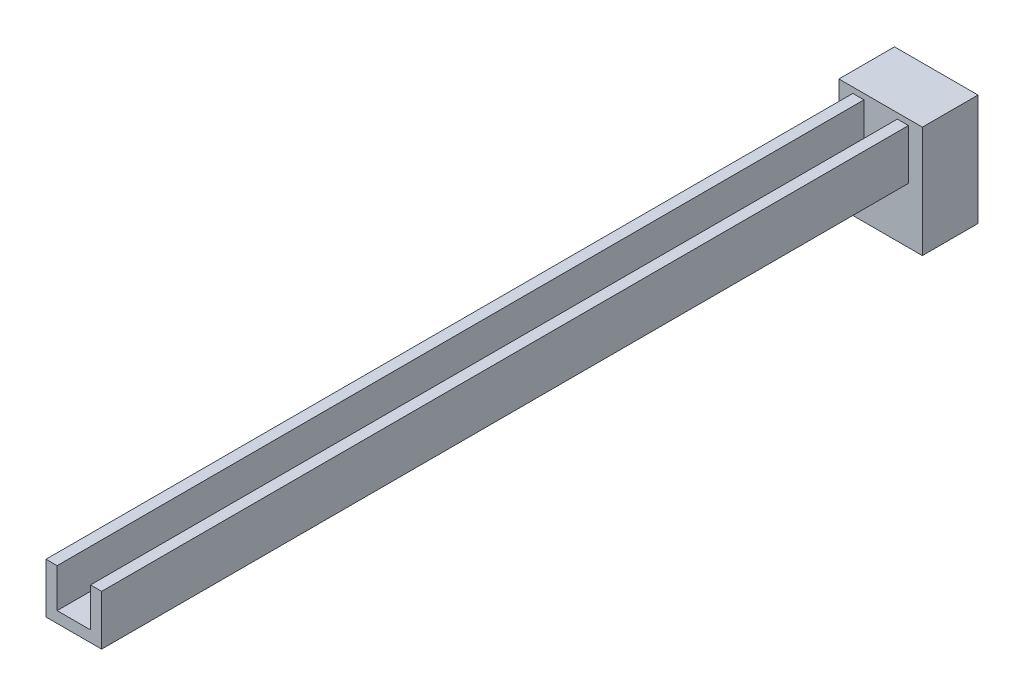
SolidWorks part; units mm, degrees
ref_plane "正面" through (0, 0, 0) normal (0, 0, 1) x (1, 0, 0)
ref_plane "平面" through (0, 0, 0) normal (0, 1, 0) x (1, 0, 0)
ref_plane "右側面" through (0, 0, 0) normal (1, 0, 0) x (0, 0, -1)
sketch "ｽｹｯﾁ1" plane through (0, 0, 0) normal (0, 0, 1) x (1, 0, 0)
  line L0 (-5, 9) -> (-5, 0)
  line L1 (-5, 0) -> (5, 0)
  line L2 (5, 0) -> (5, 9)
  line L3 (5, 9) -> (3, 9)
  line L4 (3, 9) -> (3, 2)
  line L5 (3, 2) -> (-3, 2)
  line L6 (-3, 2) -> (-3, 9)
  line L7 (-3, 9) -> (-5, 9)
  dimension "D1" = 9
  dimension "D2" = 9
  dimension "D3" = 10
  dimension "D4" = 5
  dimension "D5" = 2
  dimension "D6" = 2
  dimension "D7" = 2
extrude "ﾎﾞｽ - 押し出し1" add sketch "ｽｹｯﾁ1" along normal blind 245
sketch "ｽｹｯﾁ2" plane through (0, 0, 0) normal (0, -1, 0) x (1, 0, 0)
  line L0 (-5, 245) -> (5, 245) construction
  circle A0 centre (0, 225) radius 2.5
  circle A1 centre (0, 217) radius 2.5
  circle A2 centre (0, 122.5) radius 2.5
  circle A3 centre (0, 209) radius 2.5
  circle A4 centre (0, 193) radius 2.5
  circle A5 centre (0, 161) radius 2.5
  dimension "D1" = 20
  dimension "D3" = 5
  dimension "D4" = 5
  dimension "D5" = 5
  dimension "D6" = 122.5
  dimension "D7" = 5
  dimension "D8" = 8
  dimension "D9" = 5
  dimension "D10" = 16
  dimension "D11" = 5
  dimension "D12" = 32
  dimension "D2" = 28
extrude "ｶｯﾄ - 押し出し1" cut sketch "ｽｹｯﾁ2" against normal through all
ref_plane "平面1" through (0, 0, 122.5) normal (0, 0, 1) x (1, 0, 0)
mirror "ﾐﾗｰ1" about plane through (0, 0, 122.5) normal (0, 0, 1) of "ｶｯﾄ - 押し出し1"
sketch "ｽｹｯﾁ3" plane through (0, 0, 0) normal (0, -1, 0) x (1, 0, 0)
  line L0 (-5, 0) -> (-5, 100)
  line L1 (-5, 245) -> (-5, 0) construction
  line L2 (-5, 100) -> (5, 100)
  line L3 (5, 245) -> (5, 0) construction
  line L4 (5, 100) -> (5, 0)
  line L5 (5, 0) -> (-5, 0)
  dimension "D1" = 100
extrude "ｶｯﾄ - 押し出し2" cut sketch "ｽｹｯﾁ3" against normal through all both
sketch "ｽｹｯﾁ5" plane through (0, 0, 100) normal (0, 0, -1) x (-1, 0, 0)
  line L0 (-7.5, 10) -> (-7.5, -10)
  line L1 (-7.5, -10) -> (7.5, -10)
  line L2 (7.5, -10) -> (7.5, 10)
  line L3 (7.5, 10) -> (-7.5, 10)
  dimension "D1" = 15
  dimension "D2" = 7.5
  dimension "D3" = 20
  dimension "D4" = 10
extrude "ﾎﾞｽ - 押し出し3" add sketch "ｽｹｯﾁ5" along normal blind 10
equation "\"D2@ｽｹｯﾁ5\"=\"D1@ｽｹｯﾁ5\"/2"
